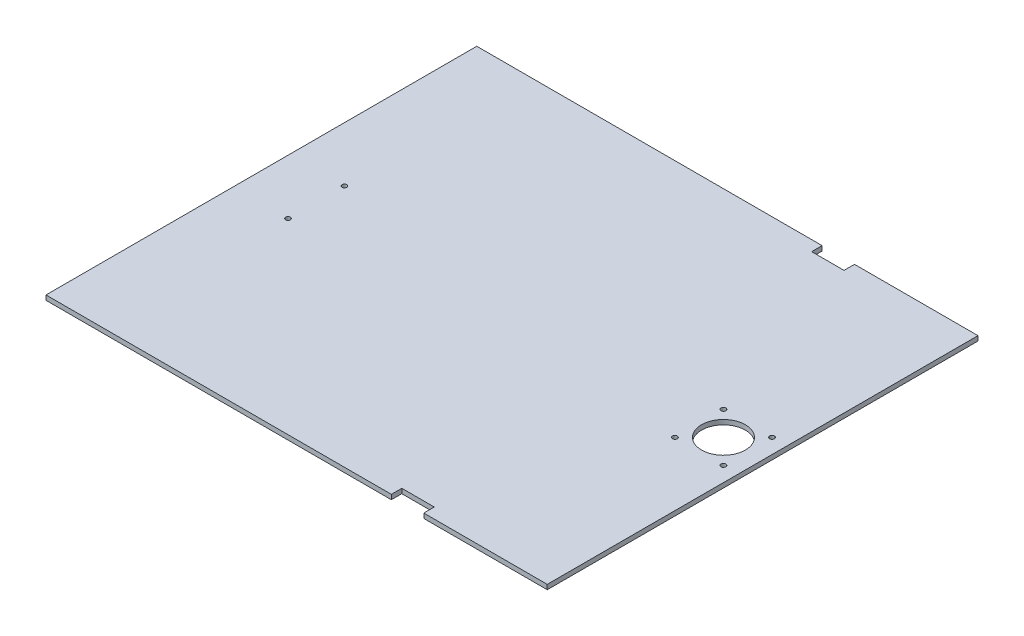
SolidWorks part; units mm, degrees
material "Acrílico (Impacto medio-alto)"
ref_plane "Alzado" through (0, 0, 0) normal (0, 0, 1) x (1, 0, 0)
ref_plane "Planta" through (0, 0, 0) normal (0, 1, 0) x (1, 0, 0)
ref_plane "Vista lateral" through (0, 0, 0) normal (1, 0, 0) x (0, 0, -1)
sketch "Sketch1" plane through (0, 0, 0) normal (0, 1, 0) x (1, 0, 0)
  line L1 (-160, -137.5) -> (160, -137.5)
  line L2 (-160, -137.5) -> (-160, 137.5)
  line L3 (-160, 137.5) -> (160, 137.5)
  line L4 (160, -137.5) -> (160, 137.5)
  line L5 (-160, -137.5) -> (160, 137.5) construction
  line L6 (-160, 137.5) -> (160, -137.5) construction
  point P0 (0, 0)
  dimension "D1" = 320
  dimension "D2" = 275
extrude "Boss-Extrude1" add sketch "Sketch1" along normal blind 3
sketch "Sketch2" plane through (0, 3, 0) normal (0, 1, 0) x (1, 0, 0)
  line L0 (0, 0) -> (160, 0) construction
  line L1 (160, -137.5) -> (160, 137.5) construction
  line L3 (119.5, -15.5) -> (150.5, -15.5)
  line L4 (119.5, -15.5) -> (119.5, 15.5)
  line L5 (119.5, 15.5) -> (150.5, 15.5)
  line L6 (150.5, -15.5) -> (150.5, 15.5)
  line L7 (119.5, -15.5) -> (150.5, 15.5) construction
  line L8 (119.5, 15.5) -> (150.5, -15.5) construction
  point P5 (135, 0)
  dimension "D1" = 31
  dimension "D2" = 31
  dimension "D3" = 25
sketch "Sketch3" plane through (0, 3, 0) normal (0, 1, 0) x (1, 0, 0)
  point P0 (150.5, 15.5)
  point P3 (150.5, -15.5)
  point P6 (119.5, -15.5)
  point P9 (119.5, 15.5)
hole_wizard "Taladro de margen para M2.51" positions "Sketch3" profile "Sketch4" hole size "M2.5" standard "ISO" end condition through all
sketch "Sketch4" plane through (150.5, 3, -15.5) normal (1, 0, 0) x (0, 0, 1)
  line L0 (0, 0) -> (0, 3)
  line L1 (0, 3) -> (1.55, 3)
  line L2 (1.55, 3) -> (1.55, 0)
  line L5 (1.55, 0) -> (0, 0)
  line L11 (0, -6.35) -> (0, 107.95) construction
  dimension "Diámetro de taladro hasta el siguiente" = 3.1
  dimension "Profundidad de taladro hasta el siguiente" = 3
sketch "Sketch6" plane through (0, 3, 0) normal (0, 1, 0) x (1, 0, 0)
  line L0 (0, 0) -> (-160, 0) construction
  line L1 (-160, 137.5) -> (-160, -137.5) construction
  line L2 (-125, 0) -> (-125, 18) construction
  line L3 (-125, 0) -> (-125, -18) construction
  circle A0 centre (-125, -18) radius 1.5
  circle A1 centre (-125, 18) radius 1.5
  dimension "D2" = 3
  dimension "D3" = 3
  dimension "D1" = 36
  dimension "D4" = 35
extrude "Cut-Extrude1" cut sketch "Sketch6" against normal through all
sketch "Sketch7" plane through (0, 3, 0) normal (0, 1, 0) x (1, 0, 0)
  line L0 (119.5, 15.5) -> (150.5, 15.5) construction
  line L1 (135, 15.5) -> (135, 0) construction
  line L2 (150.5, -15.5) -> (150.5, 15.5) construction
  circle A0 centre (135, 0) radius 14
  point P11 (150.5, 0)
  dimension "D1" = 28
extrude "Cut-Extrude2" cut sketch "Sketch7" against normal blind 10
sketch "Sketch8" plane through (0, 3, 0) normal (0, 1, 0) x (1, 0, 0)
  line L0 (-160, -137.5) -> (160, -137.5) construction
  line L1 (81.1651, -137.5) -> (60.4734, -137.5)
  line L2 (81.1651, -137.5) -> (81.1651, -130.8276)
  line L3 (81.1651, -130.8276) -> (60.4734, -130.8276)
  line L4 (60.4734, -137.5) -> (60.4734, -130.8276)
  line L5 (-840, 0) -> (49160, 0) construction
  line L6 (160, -137.5) -> (160, 137.5) construction
  line L7 (81.1651, 137.5) -> (81.1651, 130.8276)
  line L8 (60.4734, 137.5) -> (60.4734, 130.8276)
  line L9 (81.1651, 130.8276) -> (60.4734, 130.8276)
  line L10 (60.4734, 137.5) -> (81.1651, 137.5)
  point P11 (160, 0)
extrude "Cut-Extrude3" cut sketch "Sketch8" against normal blind 10
